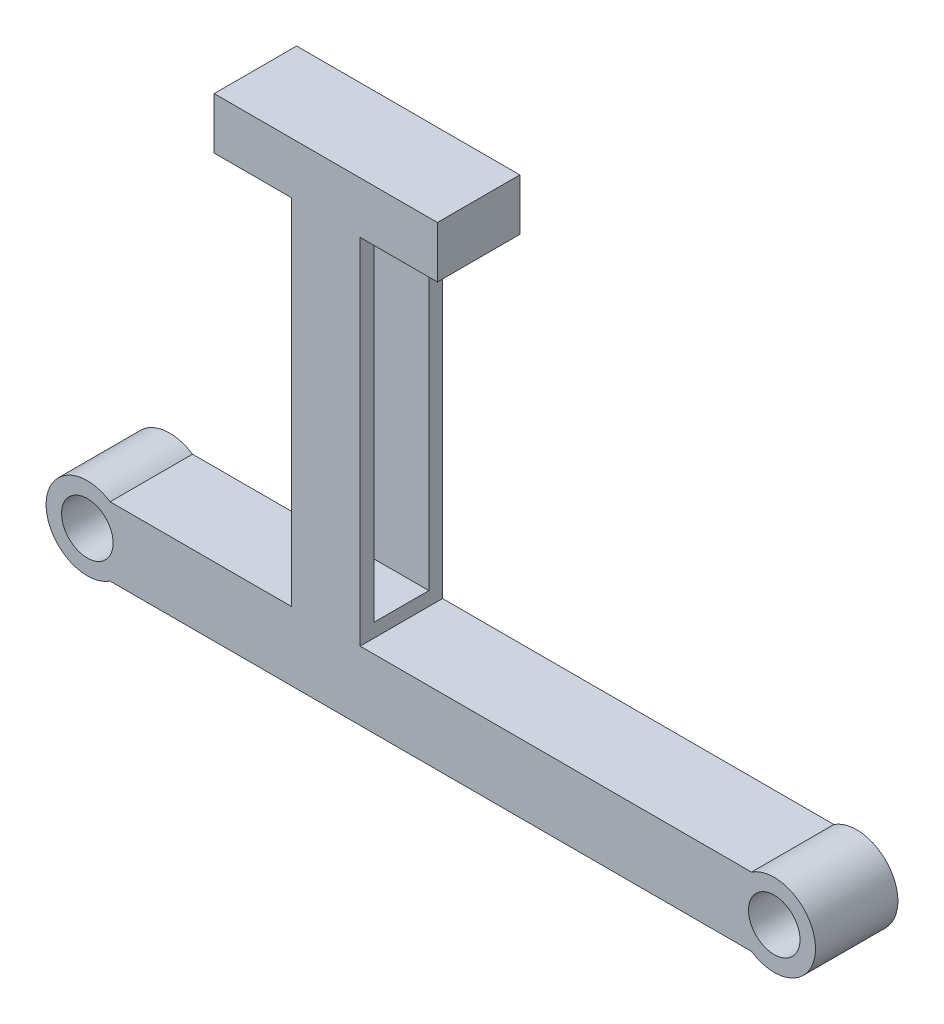
SolidWorks part; units mm, degrees
ref_plane "Front Plane" through (0, 0, 0) normal (0, 0, 1) x (1, 0, 0)
ref_plane "Top Plane" through (0, 0, 0) normal (0, 1, 0) x (1, 0, 0)
ref_plane "Right Plane" through (0, 0, 0) normal (1, 0, 0) x (0, 0, -1)
sketch "Sketch1" plane through (0, 0, 0) normal (0, 0, 1) x (1, 0, 0)
  line L0 (-55.7179, -3.2527) -> (144.2821, -3.2527)
  line L1 (-49.0846, 6.7473) -> (137.6489, 6.7473)
  line L2 (137.6489, -13.2527) -> (-49.0846, -13.2527)
  line L3 (13.7121, 109.8173) -> (13.7121, 6.7473)
  line L4 (3.7121, 6.7473) -> (23.7121, 6.7473)
  line L5 (3.7121, 6.7473) -> (3.7121, 109.8173)
  line L6 (3.7121, 109.8173) -> (23.7121, 109.8173)
  line L7 (23.7121, 6.7473) -> (23.7121, 109.8173)
  line L13 (-18.7879, 109.8173) -> (46.2121, 109.8173)
  line L14 (-18.7879, 109.8173) -> (-18.7879, 124.8173)
  line L15 (-18.7879, 124.8173) -> (46.2121, 124.8173)
  line L16 (46.2121, 109.8173) -> (46.2121, 124.8173)
  circle A0 centre (-55.7179, -3.2527) radius 7.5
  circle A1 centre (-55.7179, -3.2527) radius 12
  circle A2 centre (144.2821, -3.2527) radius 7.5
  circle A3 centre (144.2821, -3.2527) radius 12
  dimension "D2" = 15
  dimension "D3" = 24
  dimension "D4" = 24
  dimension "D5" = 15
  dimension "D1" = 200
  dimension "D6" = 20
  dimension "D7" = 10
  dimension "D8" = 69.43
  dimension "D9" = 20
  dimension "D10" = 65
  dimension "D11" = 32.5
  dimension "D12" = 15
  dimension "D13" = 103.07
extrude "Boss-Extrude1" add sketch "Sketch1" along normal blind 12 and the other way blind 12 contours A3 L1 A1 L0 | A3 L0 A1 L2 | A1 | A3 | A2 | A0 | L5 L4 L7 L6 | L14 L13 L16 L15 region at (44.2821, 1.794, 0) region at (44.2821, -8.2993, 0)
sketch "Sketch2" plane through (23.7121, 0, 0) normal (1, 0, 0) x (0, 0, -1)
  line L4 (-12, 6.7473) -> (12, 6.7473)
  line L5 (12, 6.7473) -> (12, 109.8173)
  line L6 (12, 109.8173) -> (-12, 109.8173)
  line L7 (-12, 109.8173) -> (-12, 6.7473)
  line L8 (-12, 6.7473) -> (12, 6.7473)
  line L9 (12, 6.7473) -> (12, 109.8173)
  line L10 (12, 109.8173) -> (-12, 109.8173)
  line L11 (-12, 109.8173) -> (-12, 6.7473)
  line L24 (-8, 10.7473) -> (8, 10.7473)
  line L25 (8, 10.7473) -> (8, 105.8173)
  line L26 (8, 105.8173) -> (-8, 105.8173)
  line L27 (-8, 105.8173) -> (-8, 10.7473)
  line L28 (-8, 10.7473) -> (8, 10.7473)
  line L29 (8, 10.7473) -> (8, 105.8173)
  line L30 (8, 105.8173) -> (-8, 105.8173)
  line L31 (-8, 105.8173) -> (-8, 10.7473)
  dimension "D1" = 0
  dimension "D2" = 4
extrude "Cut-Extrude1" cut sketch "Sketch2" against normal through all both and the other way through all contours L28 L29 L30 L31
